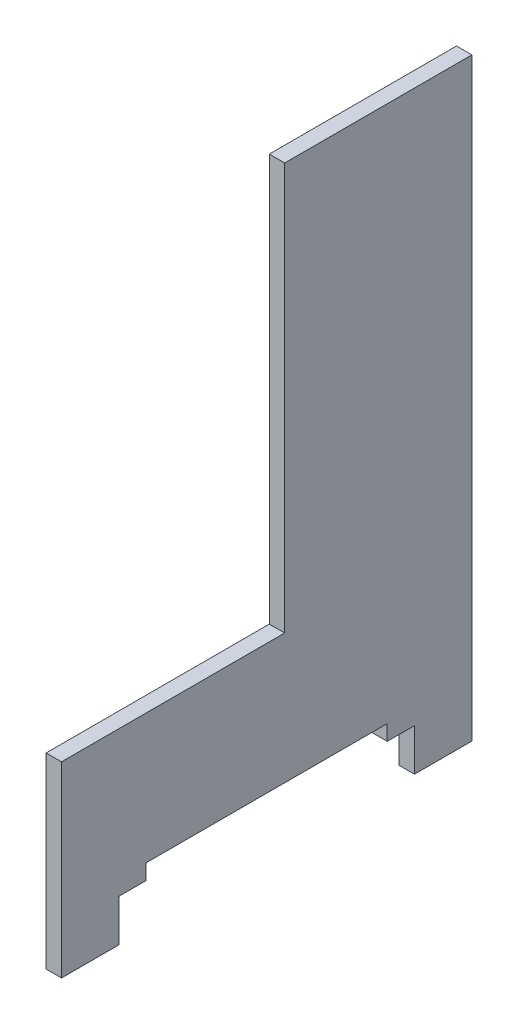
SolidWorks part; units mm, degrees
ref_plane "Front Plane" through (0, 0, 0) normal (0, 0, 1) x (1, 0, 0)
ref_plane "Top Plane" through (0, 0, 0) normal (0, 1, 0) x (1, 0, 0)
ref_plane "Right Plane" through (0, 0, 0) normal (1, 0, 0) x (0, 0, -1)
sketch "Sketch1" plane through (0, 0, 0) normal (0, 1, 0) x (1, 0, 0)
  line L0 (0, 0) -> (0, 40) construction
  line L1 (-40, 40) -> (40, 40) construction
  line L2 (-40, 40) -> (-40, -40) construction
  line L3 (-40, -40) -> (40, -40) construction
  line L4 (40, 40) -> (40, -40) construction
  line L5 (0, 0) -> (-40, 0) construction
  line L6 (-20, 60) -> (60, 60) construction
  line L7 (-37, -37) -> (37, -37) construction
  line L8 (37, 37) -> (37, -37) construction
  line L9 (-37, 37) -> (37, 37) construction
  line L10 (-37, 37) -> (-37, -37) construction
  line L11 (-37, -37) -> (-40, -37) construction
  line L12 (14.7, 20) -> (17.7, 20) construction
  line L13 (40, -31.8) -> (-40, -31.8) construction
  line L14 (-40, -28.8) -> (40, -28.8) construction
  line L15 (-40, -23.5) -> (40, -23.5) construction
  line L16 (0, -31.8) -> (0, -28.8) construction
  line L17 (0, -31.8) -> (0, -40) construction
  line L18 (0, -28.8) -> (0, -23.5) construction
  line L19 (43.5, 20) -> (48.8, 20) construction
  line L20 (51.8, 20) -> (60, 20) construction
  line L21 (40, 2.3) -> (-40, 2.3) construction
  line L22 (-40, 5.3) -> (40, 5.3) construction
  line L23 (3, 5.3) -> (3, 2.3) construction
  line L25 (40, -0.7) -> (-40, -0.7) construction
  line L26 (40, 8.3) -> (-40, 8.3) construction
  line L27 (3, 2.3) -> (3, -0.7) construction
  line L28 (3, 5.3) -> (3, 8.3) construction
  line L29 (17.7, 20) -> (20.7, 20) construction
  line L30 (19, 20) -> (56.5, 20) construction
  line L31 (3, 0) -> (0, 0) construction
  line L33 (40, 31.8) -> (-40, 31.8) construction
  line L34 (-40, 28.8) -> (40, 28.8) construction
  line L35 (-40, 23.5) -> (40, 23.5) construction
  line L36 (6, 2.3) -> (6, 1) construction
  line L37 (6, -36.5) -> (6, -40) construction
  line L38 (56.5, 20) -> (60, 20) construction
  line L40 (3, 0) -> (6, 0) construction
  line L41 (6, 1) -> (6, -36.5) construction
  line L42 (19, 20) -> (17.7, 20) construction
sketch "Sketch2" plane through (0, 0, 0) normal (1, 0, 0) x (0, 0, -1)
  line L0 (40, 0) -> (-40, 0) construction
  line L1 (40, 3.55) -> (-40, 3.55)
  line L2 (40, 3.55) -> (40, 119.407)
  line L3 (40, 119.407) -> (-40, 119.407) construction
  line L4 (-40, 3.55) -> (-40, 119.407) construction
  line L5 (40, -3.55) -> (-40, -3.55) construction
  line L6 (0, 0) -> (0, 119.407) construction
  line L7 (20, -5.5) -> (20, -47.5) construction
  line L8 (5.3, 47.5) -> (2.3, 47.5)
  line L9 (5.3, 47.5) -> (5.3, 5.5)
  line L10 (5.3, 5.5) -> (2.3, 5.5)
  line L11 (2.3, 47.5) -> (2.3, 5.5)
  line L12 (5.3, 5.5) -> (5.3, 3.55) construction
  line L13 (20, -5.5) -> (20, -3.55) construction
  line L14 (5.3, 26.5) -> (-36.5, 26.5) construction
  line L15 (20, -16.45) -> (20, -36.55) construction
  line L16 (-36.5, 36.55) -> (1, 36.55)
  line L17 (-36.5, 36.55) -> (-36.5, 16.45)
  line L18 (-36.5, 16.45) -> (1, 16.45)
  line L19 (1, 36.55) -> (1, 16.45)
  line L20 (37, 116.407) -> (37, 6.55) construction
  line L21 (37, 6.55) -> (-37, 6.55) construction
  line L22 (-37, 6.55) -> (-37, 116.407) construction
  line L23 (-37, 6.55) -> (-37, 3.55) construction
  line L24 (-37, 6.55) -> (-40, 6.55) construction
  line L25 (-23.5, 3.55) -> (-23.5, 6.55)
  line L26 (-23.5, 6.55) -> (-28.8, 6.55)
  line L27 (-28.8, 6.55) -> (-28.8, 11.75)
  line L28 (-28.8, 11.75) -> (-23.5, 11.75)
  line L29 (-23.5, 11.75) -> (-23.5, 14.75)
  line L30 (-23.5, 14.75) -> (-40, 14.75)
  line L31 (-31.8, 14.75) -> (-31.8, 3.55) construction
  line L32 (20, -6.55) -> (20, -11.75) construction
  line L33 (31.8, 14.75) -> (31.8, 3.55) construction
  line L34 (23.5, 14.75) -> (40, 14.75)
  line L35 (23.5, 11.75) -> (23.5, 14.75)
  line L36 (28.8, 11.75) -> (23.5, 11.75)
  line L37 (28.8, 6.55) -> (28.8, 11.75)
  line L38 (23.5, 6.55) -> (28.8, 6.55)
  line L39 (23.5, 3.55) -> (23.5, 6.55)
  line L40 (23.5, 14.75) -> (-23.5, 14.75) construction
  line L41 (37, 116.407) -> (-37, 116.407) construction
  line L43 (3.5, 119.407) -> (3.5, 40.05) construction
  line L44 (-37, 116.407) -> (-37, 119.407) construction
  line L45 (-37, 116.407) -> (-40, 116.407) construction
  line L46 (3.5, 40.05) -> (-40, 40.05)
  line L47 (6.5, 119.407) -> (6.5, 37.05) construction
  line L48 (6.5, 37.05) -> (-40, 37.05) construction
  line L49 (3.5, 40.05) -> (3.5, 37.05) construction
  line L50 (3.5, 40.05) -> (6.5, 40.05) construction
  line L51 (27.1, 60.107) -> (7, 60.107) construction
  line L52 (6.5, 37.05) -> (6.5, 3.55) construction
  line L53 (-36.5, 36.55) -> (-37, 36.55) construction
  line L54 (-36.5, 36.55) -> (-36.5, 37.05) construction
  line L55 (3.5, 37.05) -> (3.5, 3.55) construction
  line L56 (27.1, 60.107) -> (7, 60.107) construction
  line L57 (27.1, 60.107) -> (27.1, 114.407) construction
  line L58 (27.1, 114.407) -> (7, 114.407) construction
  line L59 (7, 60.107) -> (7, 114.407) construction
  line L60 (27.1, 114.407) -> (7, 114.407) construction
  line L61 (27.1, 107.657) -> (27.1, 66.857) construction
  line L62 (7, 107.657) -> (7, 66.857) construction
  line L63 (3.5, 98.4639) -> (6.5, 98.4639) construction
  line L64 (3.5, 55.3502) -> (6.5, 55.3502) construction
  circle A0 centre (17.05, 76.907) radius 21 construction
  circle A1 centre (17.05, 76.907) radius 21 construction
  circle A2 centre (17.05, 76.907) radius 24 construction
  dimension "D2" = 3
  dimension "D1" = 0.5
  dimension "D3" = 2
  dimension "D4" = 43.5
ref_plane "xslide" through (0, 26.5, 0) normal (0, 1, 0) x (1, 0, 0)
ref_plane "xgear" through (0, 0, -2.3) normal (0, 0, 1) x (1, 0, 0)
sketch "Sketch3" plane through (0, 0, 0) normal (0, 1, 0) x (1, 0, 0)
  line L0 (28.8, 31.8) -> (23.5, 31.8)
  line L1 (40, 40) -> (-40, 40)
  line L2 (40, 40) -> (40, -40)
  line L3 (40, -40) -> (-40, -40)
  line L4 (-40, 40) -> (-40, -40)
  line L5 (37, 37) -> (-37, 37) construction
  line L6 (37, 37) -> (37, -37) construction
  line L7 (37, -37) -> (-37, -37) construction
  line L8 (-37, 37) -> (-37, -37) construction
  line L9 (23.5, 31.8) -> (23.5, 28.8)
  line L10 (23.5, 28.8) -> (40, 28.8)
  line L11 (28.8, 31.8) -> (28.8, 37)
  line L12 (0, 0) -> (0, 40) construction
  line L13 (0, 0) -> (-40, 0) construction
  line L14 (-31.8, 28.8) -> (-31.8, 40)
  line L15 (-23.5, 28.8) -> (-40, 28.8)
  line L16 (-26.15, 31.8) -> (-26.15, 17.05) construction
  line L17 (31.8, 28.8) -> (31.8, 40)
  line L18 (-23.5, 31.8) -> (-23.5, 28.8)
  line L19 (28.8, 37) -> (23.5, 37)
  line L20 (23.5, 37) -> (23.5, 40)
  line L21 (28.8, 31.8) -> (31.8, 31.8) construction
  line L22 (31.8, 31.8) -> (40, 31.8) construction
  line L23 (37, 37) -> (40, 37) construction
  line L24 (48.8, 20) -> (54, 20) construction
  line L25 (51.8, 20) -> (60, 20) construction
  line L26 (48.8, 20) -> (43.5, 20) construction
  line L27 (-28.8, 31.8) -> (-23.5, 31.8)
  line L28 (-28.8, 31.8) -> (-28.8, 37)
  line L29 (-28.8, 37) -> (-23.5, 37)
  line L30 (-23.5, 37) -> (-23.5, 40)
  line L31 (23.5, 28.8) -> (-23.5, 28.8) construction
  line L32 (8.3, -6.95) -> (8.3, 41.05) construction
  line L33 (5.3, -3.95) -> (2.3, -3.95)
  line L34 (5.3, -3.95) -> (5.3, 38.05)
  line L35 (5.3, 38.05) -> (2.3, 38.05)
  line L36 (2.3, -3.95) -> (2.3, 38.05)
  line L37 (-26.15, 2.3) -> (-26.15, 0) construction
  line L38 (14.7, 20) -> (-27.3, 20) construction
  line L39 (-6.15, 20) -> (8.6, 20) construction
  line L40 (5.3, 17.05) -> (2.3, 17.05) construction
  line L41 (2.3, 17.05) -> (1, 17.05) construction
  line L42 (1, 17.05) -> (-36.5, 17.05) construction
  line L43 (19, 20) -> (17.7, 20) construction
  line L44 (19, 20) -> (56.5, 20) construction
  line L45 (56.5, 20) -> (76.6, 20) construction
  line L46 (-36.5, 7) -> (1, 7)
  line L47 (-36.5, 7) -> (-36.5, 27.1)
  line L48 (-36.5, 27.1) -> (1, 27.1)
  line L49 (1, 7) -> (1, 27.1)
  line L50 (8.3, 41.05) -> (-0.7, 41.05) construction
  line L51 (-0.7, -6.95) -> (-0.7, 41.05) construction
  line L52 (8.3, -6.95) -> (-0.7, -6.95) construction
  line L53 (5.3, 38.05) -> (8.3, 38.05) construction
  line L54 (14.7, 20) -> (11.7, 20) construction
  line L55 (40, 2.3) -> (-40, 2.3) construction
  line L57 (2.3, 38.05) -> (0, 38.05) construction
ref_plane "zgear" through (2.3, 0, 0) normal (1, 0, 0) x (0, 0, -1)
ref_plane "zslide" through (0, 0, -17.05) normal (0, 0, 1) x (1, 0, 0)
ref_plane "zstop" through (0, 14.75, 0) normal (0, 1, 0) x (1, 0, 0)
ref_plane "peak_left" through (-40, 0, 0) normal (1, 0, 0) x (0, 0, -1)
ref_plane "peak_right" through (40, 0, 0) normal (1, 0, 0) x (0, 0, -1)
ref_plane "peak_front" through (0, 0, -40) normal (0, 0, 1) x (1, 0, 0)
ref_plane "peak_back" through (0, 0, 40) normal (0, 0, 1) x (1, 0, 0)
ref_plane "peak_uno" through (0, 0, -3.5) normal (0, 0, 1) x (1, 0, 0)
ref_plane "peak_top" through (0, 119.407, 0) normal (0, 1, 0) x (1, 0, 0)
ref_plane "peak_bottom" through (0, 3.55, 0) normal (0, 1, 0) x (1, 0, 0)
sketch "Sketch4" plane through (-40, 0, 0) normal (1, 0, 0) x (0, 0, -1)
  line L0 (40, 119.407) -> (40, 3.55)
  line L1 (40, 3.55) -> (28.8, 3.55)
  line L2 (28.8, 3.55) -> (28.8, 11.75)
  line L3 (28.8, 11.75) -> (23.5, 11.75)
  line L4 (23.5, 11.75) -> (23.5, 14.75)
  line L5 (23.5, 14.75) -> (-23.5, 14.75)
  line L6 (-23.5, 14.75) -> (-23.5, 11.75)
  line L7 (-23.5, 11.75) -> (-28.8, 11.75)
  line L8 (-28.8, 11.75) -> (-28.8, 3.55)
  line L9 (-28.8, 3.55) -> (-40, 3.55)
  line L10 (-40, 3.55) -> (-40, 40.05)
  line L11 (-40, 40.05) -> (3.5, 40.05)
  line L12 (3.5, 40.05) -> (3.5, 119.407)
  line L13 (3.5, 119.407) -> (40, 119.407)
  line L14 (40, 119.407) -> (-40, 119.407) construction
  line L15 (40, 3.55) -> (-40, 3.55) construction
  line L16 (40, 3.55) -> (40, 119.407) construction
  line L17 (-40, 3.55) -> (-40, 119.407) construction
  line L18 (3.5, 40.05) -> (-40, 40.05) construction
  line L19 (3.5, 119.407) -> (3.5, 40.05) construction
  line L20 (23.5, 14.75) -> (-23.5, 14.75) construction
  line L21 (23.5, 11.75) -> (23.5, 14.75) construction
  line L22 (-23.5, 11.75) -> (-23.5, 14.75) construction
  line L23 (-28.8, 6.55) -> (-28.8, 11.75) construction
  line L24 (28.8, 6.55) -> (28.8, 11.75) construction
  line L25 (28.8, 11.75) -> (23.5, 11.75) construction
  line L26 (-28.8, 11.75) -> (-23.5, 11.75) construction
sketch "Sketch5" plane through (0, 0, -40) normal (0, 0, 1) x (1, 0, 0)
  line L1 (-40, 119.407) -> (-37, 119.407)
  line L2 (-40, 119.407) -> (-40, 3.55)
  line L3 (-40, 3.55) -> (-37, 3.55)
  line L4 (-37, 119.407) -> (-37, 3.55)
extrude "Boss-Extrude1" add sketch "Sketch4" along normal up to vertex (3 mm away) up to point (-37, 3.55, -40)
